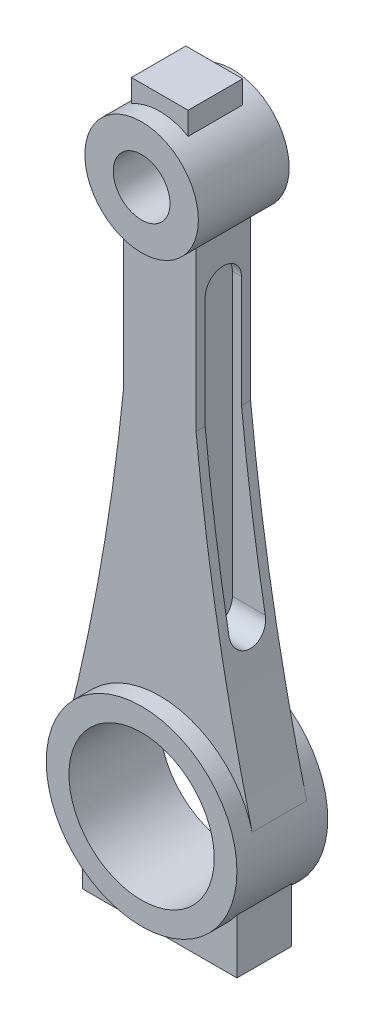
SolidWorks part; units mm, degrees
ref_plane "Front Plane" through (0, 0, 0) normal (0, 0, 1) x (1, 0, 0)
ref_plane "Top Plane" through (0, 0, 0) normal (0, 1, 0) x (1, 0, 0)
ref_plane "Right Plane" through (0, 0, 0) normal (1, 0, 0) x (0, 0, -1)
sketch "Sketch2" plane through (0, 0, 0) normal (0, 0, 1) x (1, 0, 0)
  line L0 (0, 145.5328) -> (0, 0) construction
  line L1 (0, 0) -> (0, -43.2774) construction
  line L2 (-8, 110.3953) -> (-8, 75.3953)
  line L3 (8, 110.3953) -> (8, 75.3953)
  line L4 (-6.25, 135.8253) -> (6.25, 135.8253)
  line L5 (6.25, 135.8253) -> (6.25, 130.8253)
  line L6 (-6.25, 135.8253) -> (-6.25, 130.8253)
  line L7 (-17, -12.3288) -> (-17, -24.3288)
  line L8 (-17, -24.3288) -> (17, -24.3288)
  line L9 (17, -24.3288) -> (17, -12.3288)
  circle A0 centre (0, 0) radius 16
  circle A1 centre (0, 0) radius 21
  circle A2 centre (0, 120) radius 6.25
  circle A3 centre (0, 120) radius 12.5
  arc A4 (-8, 75.3953) -> (-20.355, 5.1647) centre (-485.61, 123.2146) cw
  arc A5 (8, 75.3953) -> (20.355, 5.1647) centre (485.61, 123.2146) ccw
  dimension "D2" = 42
  dimension "D3" = 32
  dimension "D4" = 25
  dimension "D5" = 12.5
  dimension "D1" = 120
  dimension "D6" = 8
  dimension "D7" = 35
  dimension "D8" = 12.5
  dimension "D9" = 5
  dimension "D10" = 34
  dimension "D11" = 12
extrude "Boss-Extrude1" add sketch "Sketch2" along normal mid plane 20 contours A3 A2 | A1 A0 region at (-12.1021, 121.0366, 0) region at (0, 20.406, 0)
extrude "Boss-Extrude2" add sketch "Sketch2<3>" along normal mid plane 12 contours A5 L3 A3 L2 A4 A1 | A3 L5 L4 L6 | A1 L7 L8 L9 region at (0, 56.3417, 0) region at (0, 133.8599, 0) region at (0, -21.3606, 0)
sketch "Sketch2<3>" plane through (0, 0, 0) normal (0, 0, 1) x (1, 0, 0) same geometry as "Sketch2"
sketch "Sketch4" plane through (0, 0, 0) normal (1, 0, 0) x (0, 0, -1)
  line L0 (0, 100) -> (0, 38) construction
  line L1 (4, 100) -> (4, 38)
  line L2 (-4, 100) -> (-4, 38)
  line L3 (-10, 120) -> (10, 120) construction
  line L4 (-10, 132.5) -> (-10, 107.5) construction
  line L5 (10, 107.5) -> (10, 132.5) construction
  arc A0 (4, 100) -> (-4, 100) centre (0, 100) ccw
  arc A1 (-4, 38) -> (4, 38) centre (0, 38) ccw
  point P3 (0, 69)
  point P14 (0, 120)
  dimension "D2" = 4
  dimension "D1" = 62
  dimension "D3" = 20
extrude "Cut-Extrude1" cut sketch "Sketch4" against normal through all from offset 6 offset against normal yes
extrude "Cut-Extrude4" cut sketch "Sketch4<4>" along normal through all from offset 6
sketch "Sketch4<4>" plane through (0, 0, 0) normal (1, 0, 0) x (0, 0, -1) same geometry as "Sketch4"
